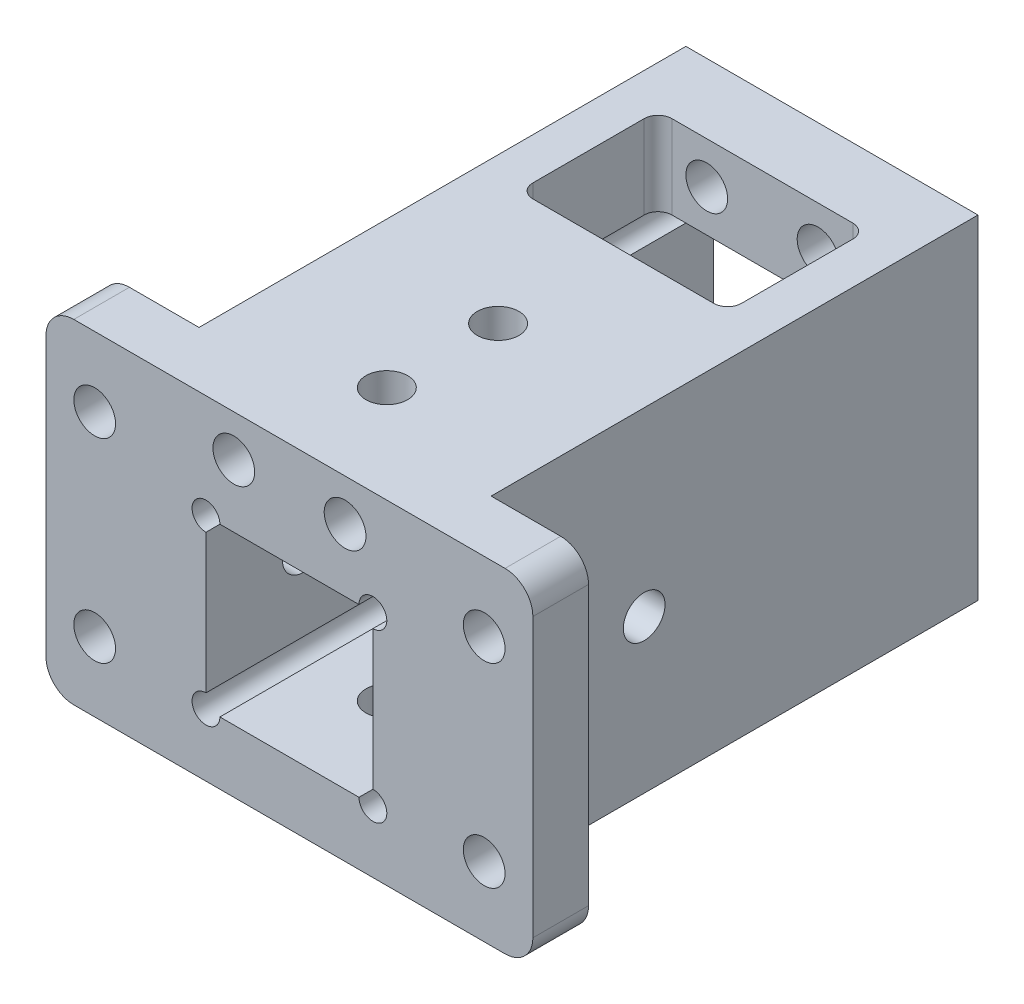
SolidWorks part; units mm, degrees
material "6061 合金"
ref_plane "前视基准面" through (0, 0, 0) normal (0, 0, 1) x (1, 0, 0)
ref_plane "上视基准面" through (0, 0, 0) normal (0, 1, 0) x (1, 0, 0)
ref_plane "右视基准面" through (0, 0, 0) normal (1, 0, 0) x (0, 0, -1)
sketch "草图1" plane through (0, 0, 0) normal (0, 0, 1) x (1, 0, 0)
  line L1 (0, 0) -> (21, 0)
  line L2 (0, 0) -> (0, 24)
  line L3 (0, 24) -> (21, 24)
  line L4 (21, 0) -> (21, 24)
  line L9 (4.5, 16.5) -> (16.5, 16.5)
  line L10 (4.5, 16.5) -> (4.5, 4.5)
  line L11 (4.5, 4.5) -> (16.5, 4.5)
  line L12 (16.5, 16.5) -> (16.5, 4.5)
  line L13 (4.5, 16.5) -> (16.5, 4.5) construction
  line L14 (4.5, 4.5) -> (16.5, 16.5) construction
  circle A0 centre (6.5, 21) radius 1.5
  circle A1 centre (14.5, 21) radius 1.5
  point P4 (10.5, 10.5)
  dimension "D6" = 3
  dimension "D7" = 3
  dimension "D8" = 3
  dimension "D9" = 8
  dimension "D10" = 4
  dimension "D1" = 24
  dimension "D2" = 21
  dimension "D3" = 12
  dimension "D4" = 13.5
  dimension "D5" = 10.5
extrude "凸台-拉伸1" add sketch "草图1" along normal blind 39
sketch "草图3" plane through (0, 0, 0) normal (-1, 0, 0) x (0, 0, 1)
  line L1 (39, 0) -> (0, 0) construction
  line L2 (39, 24) -> (39, 0) construction
  circle A0 centre (32, 11) radius 1.65
  circle A1 centre (24, 11) radius 1.65
  dimension "D1" = 3.3
  dimension "D2" = 7
  dimension "D3" = 11
  dimension "D4" = 3.3
  dimension "D5" = 8
sketch "草图5" plane through (0, 0, 39) normal (0, 0, 1) x (1, 0, 0)
  line L0 (25, 0) -> (21, 0)
  line L1 (21, 0) -> (21, 7)
  line L2 (21, 0) -> (21, 24) construction
  line L3 (21, 7) -> (25, 7)
  line L4 (0, 0) -> (21, 0) construction
  line L5 (10.5, 4.5) -> (10.5, 16.5) construction
  line L6 (4.5, 4.5) -> (16.5, 4.5) construction
  line L7 (16.5, 16.5) -> (4.5, 16.5) construction
  line L8 (0, 7) -> (-4, 7)
  line L9 (0, 0) -> (0, 7)
  line L10 (-4, 0) -> (0, 0)
  arc A0 (25, 0) -> (25, 7) centre (25, 3.5) ccw
  arc A1 (-4, 0) -> (-4, 7) centre (-4, 3.5) cw
  circle A2 centre (25, 3.5) radius 1.65
  circle A3 centre (-4, 3.5) radius 1.65
  dimension "D1" = 7
  dimension "D2" = 4
  dimension "D3" = 3.3
  dimension "D4" = 3.3
sketch "草图6" plane through (0, 0, 0) normal (0, 0, -1) x (-1, 0, 0)
  line L0 (-16.5, 4.5) -> (-16.5, 16.5) construction
  line L1 (-16.5, 4.5) -> (-16.5, 16.5) construction
  line L2 (-16.5, 16.5) -> (-4.5, 16.5) construction
  line L3 (-16.5, 16.5) -> (-4.5, 16.5) construction
  line L4 (-4.5, 16.5) -> (-4.5, 4.5) construction
  line L5 (-4.5, 4.5) -> (-16.5, 4.5) construction
  line L6 (-4.5, 16.5) -> (-4.5, 4.5) construction
  line L7 (-4.5, 4.5) -> (-16.5, 4.5) construction
  line L8 (-18, 3) -> (-18, 18)
  line L9 (-18, 18) -> (-3, 18)
  line L10 (-3, 18) -> (-3, 3)
  line L11 (-3, 3) -> (-18, 3)
  dimension "D1" = 1.5
extrude "切除-拉伸3" cut sketch "草图6" against normal blind 20
sketch "草图8" plane through (0, 0, 0) normal (0, -1, 0) x (1, 0, 0)
  line L0 (10.5, 39) -> (10.5, 32) construction
  line L1 (0, 39) -> (21, 39) construction
  line L2 (10.5, 32) -> (10.5, 24) construction
  circle A0 centre (10.5, 32) radius 1.5
  circle A1 centre (10.5, 24) radius 1.5
  dimension "D3" = 3
  dimension "D4" = 3
  dimension "D1" = 7
  dimension "D2" = 8
extrude "切除-拉伸4" cut sketch "草图8" against normal through all
sketch "草图9" plane through (0, 0, 0) normal (0, 0, -1) x (-1, 0, 0)
  line L0 (-18, 18) -> (-18, 3) construction
  line L1 (-3, 3) -> (-3, 18) construction
  line L2 (-18, 3) -> (-3, 3) construction
  line L3 (-3, 18) -> (-18, 18) construction
  circle A0 centre (-18, 4) radius 1
  circle A1 centre (-18, 17) radius 1
  circle A2 centre (-3, 4) radius 1
  circle A3 centre (-3, 17) radius 1
  dimension "D1" = 2
  dimension "D2" = 2
  dimension "D3" = 2
  dimension "D4" = 2
extrude "切除-拉伸5" cut sketch "草图9" against normal up to surface (20 mm away) up to face at (10.5, 10.5, 20)
sketch "草图10" plane through (0, 0, 0) normal (-1, 0, 0) x (0, 0, 1)
  line L0 (39, 0) -> (0, 0) construction
  line L1 (39, 24) -> (39, 0) construction
  circle A0 centre (29.5, 11) radius 4.5
  dimension "D2" = 9
  dimension "D1" = 9.5
  dimension "D3" = 11
sketch "草图12" plane through (0, 0, 0) normal (-1, 0, 0) x (0, 0, 1)
  line L0 (39, 0) -> (0, 0) construction
  circle A0 centre (10, 11) radius 4.5
  dimension "D2" = 9
  dimension "D1" = 11
sketch "草图13" plane through (0, 0, 20) normal (0, 0, -1) x (-1, 0, 0)
  circle A0 centre (-16.5, 16.5) radius 1
  circle A1 centre (-16.5, 4.5) radius 1
  circle A2 centre (-4.5, 4.5) radius 1
  circle A3 centre (-4.5, 16.5) radius 1
  dimension "D1" = 2
  dimension "D2" = 2
  dimension "D3" = 2
  dimension "D4" = 2
extrude "切除-拉伸8" cut sketch "草图13" against normal through all
sketch "草图14" plane through (0, 0, 39) normal (0, 0, 1) x (1, 0, 0)
  line L1 (0, 0) -> (-7, 0)
  line L2 (0, 0) -> (0, 24)
  line L3 (0, 24) -> (-7, 24)
  line L4 (-7, 0) -> (-7, 24)
  line L5 (21, 0) -> (28, 0)
  line L6 (21, 0) -> (21, 24)
  line L7 (21, 24) -> (28, 24)
  line L8 (28, 0) -> (28, 24)
  dimension "D1" = 24
  dimension "D2" = 7
  dimension "D3" = 24
  dimension "D4" = 7
extrude "凸台-拉伸2" add sketch "草图14" against normal blind 4
sketch "草图15" plane through (0, 0, 35) normal (0, 0, -1) x (-1, 0, 0)
  line L0 (3.5, 0) -> (3.5, 5) construction
  line L1 (7, 0) -> (0, 0) construction
  line L2 (3.5, 24) -> (3.5, 19) construction
  line L3 (0, 24) -> (7, 24) construction
  line L4 (-24.5, 0) -> (-24.5, 5) construction
  line L5 (-21, 0) -> (-28, 0) construction
  line L6 (-24.5, 24) -> (-24.5, 19) construction
  line L7 (-28, 24) -> (-21, 24) construction
  circle A0 centre (3.5, 5) radius 1.5
  circle A1 centre (3.5, 19) radius 1.5
  circle A2 centre (-24.5, 5) radius 1.5
  circle A3 centre (-24.5, 19) radius 1.5
  dimension "D3" = 3
  dimension "D4" = 3
  dimension "D7" = 3
  dimension "D8" = 3
  dimension "D1" = 5
  dimension "D2" = 5
  dimension "D5" = 5
  dimension "D6" = 5
extrude "切除-拉伸9" cut sketch "草图15" against normal through all
sketch "草图16" plane through (0, 24, 0) normal (0, 1, 0) x (1, 0, 0)
  line L0 (10.5, 0) -> (10.5, -5) construction
  line L1 (21, 0) -> (0, 0) construction
  line L2 (10.5, -5) -> (3, -5) construction
  line L4 (3, -5) -> (18, -5)
  line L5 (3, -5) -> (3, -15)
  line L6 (3, -15) -> (18, -15)
  line L7 (18, -5) -> (18, -15)
  dimension "D1" = 5
  dimension "D2" = 7.5
  dimension "D3" = 10
  dimension "D4" = 15
extrude "切除-拉伸10" cut sketch "草图16" against normal through all
sketch "草图17" plane through (0, 0, 0) normal (-1, 0, 0) x (0, 0, 1)
  line L0 (35, 0) -> (35, 11) construction
  line L1 (35, 0) -> (35, 24) construction
  line L2 (35, 11) -> (32, 11) construction
  line L3 (32, 11) -> (24, 11) construction
  circle A0 centre (32, 11) radius 1.5
  circle A1 centre (24, 11) radius 1.5
  dimension "D4" = 3
  dimension "D5" = 3
  dimension "D1" = 11
  dimension "D2" = 3
  dimension "D3" = 8
extrude "切除-拉伸11" cut sketch "草图17" against normal through all
fillet "圆角1" radius 1 8 edges at (18, 21, 5) (18, 21, 15) (3, 21, 15) (3, 21, 5) (3, 1.5, 5) (3, 1.5, 15) (18, 1.5, 5) (18, 1.5, 15)
fillet "圆角2" radius 2 4 edges at (-7, 24, 37) (28, 24, 37) (-7, 0, 37) (28, 0, 37)
chamfer "倒角1" distance 1 angle 45 5 edges at (18, 10.5, 0) (3, 10.5, 0) (19, 4, 0) (2, 4, 0) (10.5, 3, 0)
